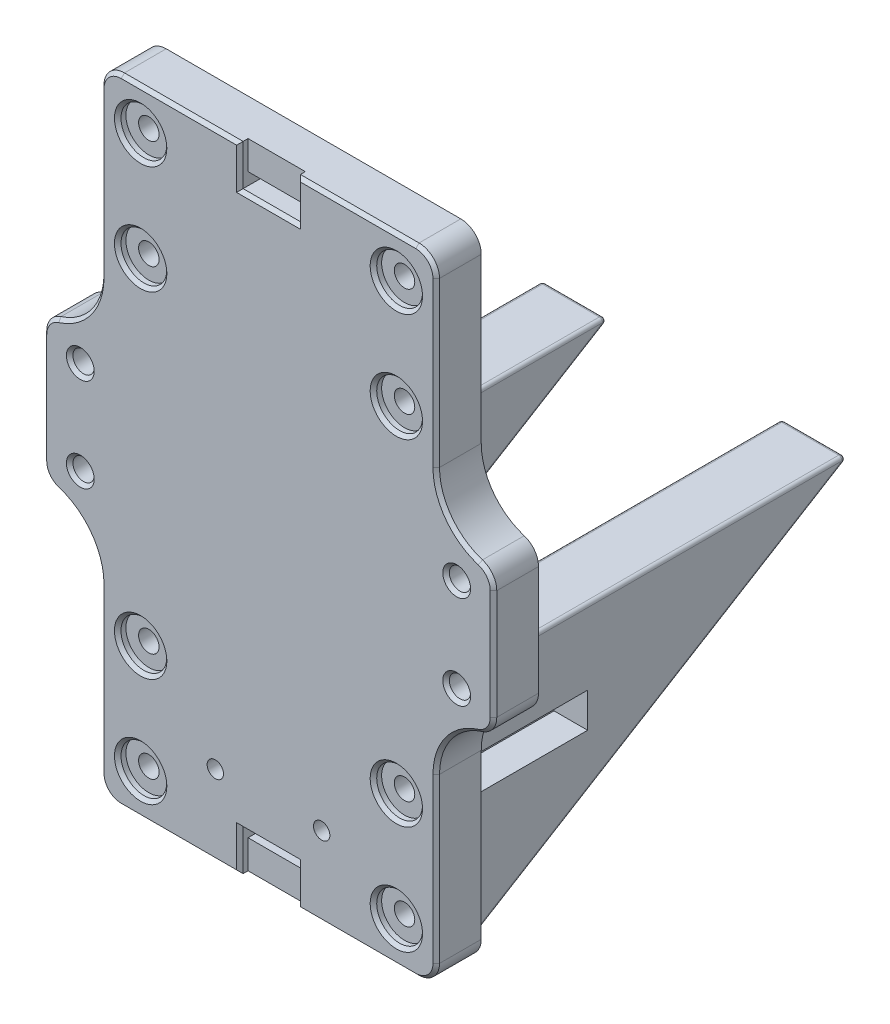
SolidWorks part; units mm, degrees
ref_plane "Front Plane" through (0, 0, 0) normal (0, 0, 1) x (1, 0, 0)
ref_plane "Top Plane" through (0, 0, 0) normal (0, 1, 0) x (1, 0, 0)
ref_plane "Right Plane" through (0, 0, 0) normal (1, 0, 0) x (0, 0, -1)
sketch "Sketch1" plane through (0, 0, 0) normal (0, 0, 1) x (1, 0, 0)
  line L1 (-31.25, -41) -> (31.25, -41) construction
  line L2 (-31.25, -41) -> (-31.25, 41) construction
  line L3 (-31.25, 41) -> (31.25, 41) construction
  line L4 (31.25, -41) -> (31.25, 41) construction
  line L5 (-31.25, -41) -> (31.25, 41) construction
  line L6 (-31.25, 41) -> (31.25, -41) construction
  line L7 (-41, -77.5) -> (41, -77.5)
  line L8 (-41, -77.5) -> (-41, 77.5)
  line L9 (-41, 77.5) -> (41, 77.5)
  line L10 (41, -77.5) -> (41, 77.5)
  line L11 (-41, -77.5) -> (41, 77.5) construction
  line L12 (-41, 77.5) -> (41, -77.5) construction
  line L13 (-31.25, -67.5) -> (31.25, -67.5) construction
  line L14 (-31.25, -67.5) -> (-31.25, 67.5) construction
  line L15 (-31.25, 67.5) -> (31.25, 67.5) construction
  line L16 (31.25, -67.5) -> (31.25, 67.5) construction
  line L17 (-31.25, -67.5) -> (31.25, 67.5) construction
  line L18 (-31.25, 67.5) -> (31.25, -67.5) construction
  circle A0 centre (31.25, 41) radius 2.5
  circle A1 centre (31.25, -41) radius 2.5
  circle A2 centre (-31.25, -41) radius 2.5
  circle A3 centre (-31.25, 41) radius 2.5
  circle A4 centre (-31.25, 67.5) radius 2.5
  circle A5 centre (31.25, 67.5) radius 2.5
  circle A6 centre (31.25, -67.5) radius 2.5
  circle A7 centre (-31.25, -67.5) radius 2.5
  point P0 (0, 0)
  point P10 (0, 0)
  point P15 (0, 0)
  dimension "D3" = 135
  dimension "D4" = 5
  dimension "D7" = 5
  dimension "D1" = 62.5
  dimension "D2" = 82
  dimension "D5" = 155
  dimension "D6" = 82
extrude "Boss-Extrude1" add sketch "Sketch1" along normal blind 11
sketch "Sketch6" plane through (0, 0, 11) normal (0, 0, 1) x (1, 0, 0)
  line L1 (-55, -18.4) -> (55, -18.4)
  line L2 (-55, -18.4) -> (-55, 18.4)
  line L3 (-55, 18.4) -> (55, 18.4)
  line L4 (55, -18.4) -> (55, 18.4)
  line L5 (-55, -18.4) -> (55, 18.4) construction
  line L6 (-55, 18.4) -> (55, -18.4) construction
  point P0 (0, 0)
  dimension "D1" = 36.8
  dimension "D2" = 110
extrude "Boss-Extrude4" add sketch "Sketch6" against normal up to surface (11 mm away) up to face at (33.75, -67.5, 0)
sketch "Sketch8" plane through (0, 0, 0) normal (0, 0, -1) x (-1, 0, 0)
  line L0 (-41, -18.4) -> (-55, -18.4) construction
  line L1 (-21, -19.4) -> (21, -19.4)
  line L2 (-21, -19.4) -> (-21, -57.4)
  line L3 (-21, -57.4) -> (21, -57.4)
  line L4 (21, -19.4) -> (21, -57.4)
  point P6 (0, -19.4)
  dimension "D1" = 38
  dimension "D2" = 42
  dimension "D3" = 1
sketch "Sketch9" plane through (0, 0, 0) normal (0, 0, -1) x (-1, 0, 0)
  line L0 (-41, 77.5) -> (41, 77.5) construction
  line L1 (-7, 70.5) -> (7, 70.5)
  line L2 (-7, 70.5) -> (-7, 67.5)
  line L3 (-7, 67.5) -> (7, 67.5)
  line L4 (7, 70.5) -> (7, 67.5)
  line L5 (-7, 70.5) -> (7, 67.5) construction
  line L6 (-7, 67.5) -> (7, 70.5) construction
  line L7 (-7, -67.5) -> (7, -67.5)
  line L8 (-7, -67.5) -> (-7, -70.5)
  line L9 (-7, -70.5) -> (7, -70.5)
  line L10 (7, -67.5) -> (7, -70.5)
  line L11 (-7, -67.5) -> (7, -70.5) construction
  line L12 (-7, -70.5) -> (7, -67.5) construction
  line L13 (41, -77.5) -> (-41, -77.5) construction
  point P0 (0, 69)
  point P5 (0, -69)
  dimension "D1" = 3
  dimension "D2" = 14
  dimension "D3" = 3
  dimension "D4" = 14
  dimension "D5" = 7
  dimension "D6" = 7
extrude "Cut-Extrude2" cut sketch "Sketch9" against normal through all
fillet "Fillet1" radius 5 8 edges at (41, -77.5, 5.5) (-41, -77.5, 5.5) (-55, -18.4, 5.5) (-55, 18.4, 5.5) (-41, 77.5, 5.5) (55, 18.4, 5.5) (55, -18.4, 5.5) (41, 77.5, 5.5)
sketch "Sketch10" plane through (0, 0, 0) normal (0, 0, -1) x (-1, 0, 0)
  line L0 (-50, 18.4) -> (-41, 18.4) construction
  line L1 (-41, -18.4) -> (-50, -18.4) construction
  line L2 (0, 48.025) -> (0, -34.9364) construction
  circle A0 centre (-46, 11.4) radius 2.6
  circle A1 centre (-46, -11.4) radius 2.6
  circle A2 centre (46, -11.4) radius 2.6
  circle A3 centre (46, 11.4) radius 2.6
  dimension "D1" = 5.2
  dimension "D2" = 5.2
  dimension "D3" = 46
  dimension "D4" = 7
  dimension "D5" = 7
extrude "Cut-Extrude3" cut sketch "Sketch10" against normal through all
fillet "Fillet3" radius 15 4 edges at (41, -18.4, 5.5) (-41, -18.4, 5.5) (-41, 18.4, 5.5) (41, 18.4, 5.5)
sketch "Sketch14" plane through (0, 0, 11) normal (0, 0, 1) x (1, 0, 0)
  circle A0 centre (31.25, -41) radius 5.6
  circle A1 centre (31.25, -67.5) radius 5.6
  circle A2 centre (31.25, 41) radius 5.6
  circle A3 centre (31.25, 67.5) radius 5.6
  circle A4 centre (-31.25, 67.5) radius 5.6
  circle A5 centre (-31.25, 41) radius 5.6
  circle A6 centre (-31.25, -41) radius 5.6
  circle A7 centre (-31.25, -67.5) radius 5.6
  dimension "D1" = 11.2
extrude "Cut-Extrude7" cut sketch "Sketch14" against normal blind 2
sketch "Sketch18" plane through (0, 0, 11) normal (0, 0, 1) x (1, 0, 0)
  line L0 (36, 77.5) -> (-36, 77.5) construction
  line L1 (-7, 70.5) -> (7, 70.5)
  line L2 (-7, 70.5) -> (-7, 77.5)
  line L3 (-7, 77.5) -> (7, 77.5)
  line L4 (7, 70.5) -> (7, 77.5)
  line L5 (-36, -77.5) -> (36, -77.5) construction
  line L6 (-7, -70.5) -> (7, -70.5)
  line L7 (-7, -70.5) -> (-7, -77.5)
  line L8 (-7, -77.5) -> (7, -77.5)
  line L9 (7, -70.5) -> (7, -77.5)
  line L10 (7, -67.5) -> (7, -70.5) construction
extrude "Cut-Extrude10" cut sketch "Sketch18" against normal blind 2
sketch "Sketch16" plane through (0, 0, 0) normal (1, 0, 0) x (0, 0, -1)
  line L0 (0, -18.5) -> (0, -76.5)
  line L1 (0, -13.4) -> (0, 13.4) construction
  line L2 (0, -72.5) -> (0, -32.4788) construction
  line L3 (0, -76.5) -> (95, -18.5)
  line L4 (95, -18.5) -> (0, -18.5)
  line L5 (0, -77.5) -> (-11, -77.5) construction
  line L6 (0, -77.5) -> (0, -72.5) construction
  point P6 (0, -72.5)
  point P8 (58.0668, -12.0762)
  point P9 (0, -76.8855)
  point P12 (0, 0)
  dimension "D1" = 59
  dimension "D2" = 95
  dimension "D3" = 1
extrude "Boss-Extrude5" add sketch "Sketch16" along normal mid plane 74
extrude "Cut-Extrude8" cut sketch "Sketch16<2>" against normal mid plane 43
sketch "Sketch16<2>" plane through (0, 0, 0) normal (1, 0, 0) x (0, 0, -1) same geometry as "Sketch16"
sketch "Sketch17" plane through (0, 0, 0) normal (0, 0, -1) x (-1, 0, 0)
  line L0 (-33.7037, -36.75) -> (-37, -36.75)
  line L1 (-28.7963, -36.75) -> (-33.7037, -36.75)
  line L2 (-33.7037, -36.75) -> (-36.1575, -41)
  line L3 (-36.1575, -41) -> (-33.7037, -45.25)
  line L4 (-33.7037, -45.25) -> (-28.7963, -45.25)
  line L5 (-28.7963, -45.25) -> (-26.3425, -41)
  line L6 (-26.3425, -41) -> (-28.7963, -36.75)
  line L7 (-28.7963, -63.25) -> (-33.7037, -63.25)
  line L8 (-33.7037, -63.25) -> (-36.1575, -67.5)
  line L9 (-36.1575, -67.5) -> (-33.7037, -71.75)
  line L10 (-33.7037, -71.75) -> (-28.7963, -71.75)
  line L11 (-28.7963, -71.75) -> (-26.3425, -67.5)
  line L12 (-26.3425, -67.5) -> (-28.7963, -63.25)
  line L13 (33.7037, -63.25) -> (28.7963, -63.25)
  line L14 (28.7963, -63.25) -> (26.3425, -67.5)
  line L15 (26.3425, -67.5) -> (28.7963, -71.75)
  line L16 (28.7963, -71.75) -> (33.7037, -71.75)
  line L17 (33.7037, -71.75) -> (36.1575, -67.5)
  line L18 (36.1575, -67.5) -> (33.7037, -63.25)
  line L19 (33.7037, -36.75) -> (28.7963, -36.75)
  line L20 (28.7963, -36.75) -> (26.3425, -41)
  line L21 (26.3425, -41) -> (28.7963, -45.25)
  line L22 (28.7963, -45.25) -> (33.7037, -45.25)
  line L23 (33.7037, -45.25) -> (36.1575, -41)
  line L24 (36.1575, -41) -> (33.7037, -36.75)
  line L25 (-37, -18.5) -> (-37, -76.5) construction
  line L26 (-37, -36.75) -> (-37, -45.25)
  line L28 (-37, -76.5) -> (-37, -18.5) construction
  line L29 (-37, -45.25) -> (-33.7037, -45.25)
  line L30 (33.7037, -36.75) -> (37, -36.75)
  line L31 (37, -18.5) -> (37, -76.5) construction
  line L32 (37, -36.75) -> (37, -45.25)
  line L33 (37, -45.25) -> (33.7037, -45.25)
  circle A4 centre (-31.25, -41) radius 4.25 construction
  circle A5 centre (-31.25, -67.5) radius 4.25 construction
  circle A6 centre (31.25, -67.5) radius 4.25 construction
  circle A7 centre (31.25, -41) radius 4.25 construction
  line M3 (-37, -76.5) -> (-37, -18.5)
  line M8 (37, -18.5) -> (37, -76.5)
  dimension "D1" = 8.5
chamfer "Chamfer2" distance 0.8 angle 45 40 edges at (-39.5355, -76.0355, 11) (-41, -52.4894, 11) (-54.0311, -16.358, 11) (-55, 0, 11) (-54.0311, 16.358, 11) (-41, 52.4894, 11) (-39.5355, 76.0355, 11) (-21.5, 77.5, 11) (21.5, 77.5, 11) (39.5355, 76.0355, 11) (41, 52.4894, 11) (54.0311, 16.358, 11) (55, 0, 11) (54.0311, -16.358, 11) (41, -52.4894, 11) (39.5355, -76.0355, 11) (-21.5, -77.5, 11) (21.5, -77.5, 11) (7, -72.5, 11) (0, -67.5, 11) (-7, -72.5, 11) (7, 72.5, 11) (-7, 72.5, 11) (0, 67.5, 11) (43.4, 11.4, 11) (43.4, -11.4, 11) (-43.4, -11.4, 11) (-43.4, 11.4, 11) (36.85, -41, 11) (-25.65, -67.5, 11) (-25.65, -41, 11) (-25.65, 41, 11) (-25.65, 67.5, 11) (36.85, 67.5, 11) (36.85, 41, 11) (36.85, -67.5, 11) (-43.9066, -23.6047, 11) (-43.9066, 23.6047, 11) (43.9066, 23.6047, 11) (43.9066, -23.6047, 11)
sketch "Sketch11" plane through (0, 0, 0) normal (0, 0, -1) x (-1, 0, 0)
  line L0 (0, 0) -> (0, -47.0529) construction
  circle A0 centre (-13, -58) radius 2
  circle A1 centre (13, -58) radius 2
  dimension "D3" = 4
  dimension "D1" = 58
  dimension "D2" = 13
extrude "Cut-Extrude4" cut sketch "Sketch11" against normal through all
sketch "Sketch12" plane through (0, 0, 0) normal (0, 0, -1) x (-1, 0, 0)
  line L1 (14.6166, -55.2) -> (11.3834, -55.2)
  line L2 (11.3834, -55.2) -> (9.7668, -58)
  line L3 (9.7668, -58) -> (11.3834, -60.8)
  line L4 (11.3834, -60.8) -> (14.6166, -60.8)
  line L5 (14.6166, -60.8) -> (16.2332, -58)
  line L6 (16.2332, -58) -> (14.6166, -55.2)
  line L7 (-11.3834, -55.2) -> (-14.6166, -55.2)
  line L8 (-14.6166, -55.2) -> (-16.2332, -58)
  line L9 (-16.2332, -58) -> (-14.6166, -60.8)
  line L10 (-14.6166, -60.8) -> (-11.3834, -60.8)
  line L11 (-11.3834, -60.8) -> (-9.7668, -58)
  line L12 (-9.7668, -58) -> (-11.3834, -55.2)
  circle A0 centre (13, -58) radius 2.8 construction
  circle A1 centre (-13, -58) radius 2.8 construction
  dimension "D1" = 5.6
  dimension "D2" = 5.6
extrude "Cut-Extrude5" cut sketch "Sketch12" against normal blind 2.6
sketch "Sketch13" plane through (0, 0, 0) normal (0, 0, -1) x (-1, 0, 0)
  line L5 (-9.525, -49) -> (9.525, -49)
  line L6 (-9.525, -49) -> (-9.525, 61)
  line L7 (-42.5, -9.525) -> (42.5, -9.525)
  line L8 (-42.5, -9.525) -> (-42.5, 9.525)
  line L9 (-42.5, 9.525) -> (42.5, 9.525)
  line L10 (42.5, -9.525) -> (42.5, 9.525)
  line L11 (-42.5, -9.525) -> (42.5, 9.525) construction
  line L12 (-42.5, 9.525) -> (42.5, -9.525) construction
  line L13 (-9.525, 61) -> (9.525, 61)
  line L14 (9.525, -49) -> (9.525, 61)
  line L15 (-9.525, -49) -> (9.525, 61) construction
  line L16 (-9.525, 61) -> (9.525, -49) construction
  point P0 (0, 0)
  point P1 (0, 6)
  point P6 (0, 0)
  point P12 (0, 0)
  point P13 (0, 0)
  point P14 (0, 0)
  dimension "D1" = 19.05
  dimension "D2" = 85
  dimension "D3" = 110
  dimension "D4" = 6
extrude "Cut-Extrude9" cut sketch "Sketch17" along normal blind 30 contours L29 L3 L2 L0 M3 | L33 L30 L24 L23 M8 | L23 L24 L19 L20 L21 L22 | L17 L18 L13 L14 L15 L16 | L11 L12 L7 L8 L9 L10 | L5 L6 L1 L2 L3 L4 region at (35.0096, -38.8294, 0) region at (31.25, -41, 0) region at (31.25, -67.5, 0) region at (-31.25, -67.5, 0) region at (-31.25, -41, 0) region at (-35.3519, -36.8412, 0)
fillet "Fillet4" radius 0.8 10 edges at (-29.25, -18.5, -95) (29.25, -18.5, -95) (-37, -18.5, -47.5) (-37, -47.5, -47.5) (-21.5, -47.5, -47.5) (-21.5, -18.5, -47.5) (21.5, -18.5, -47.5) (37, -18.5, -47.5) (21.5, -47.5, -47.5) (37, -47.5, -47.5)
